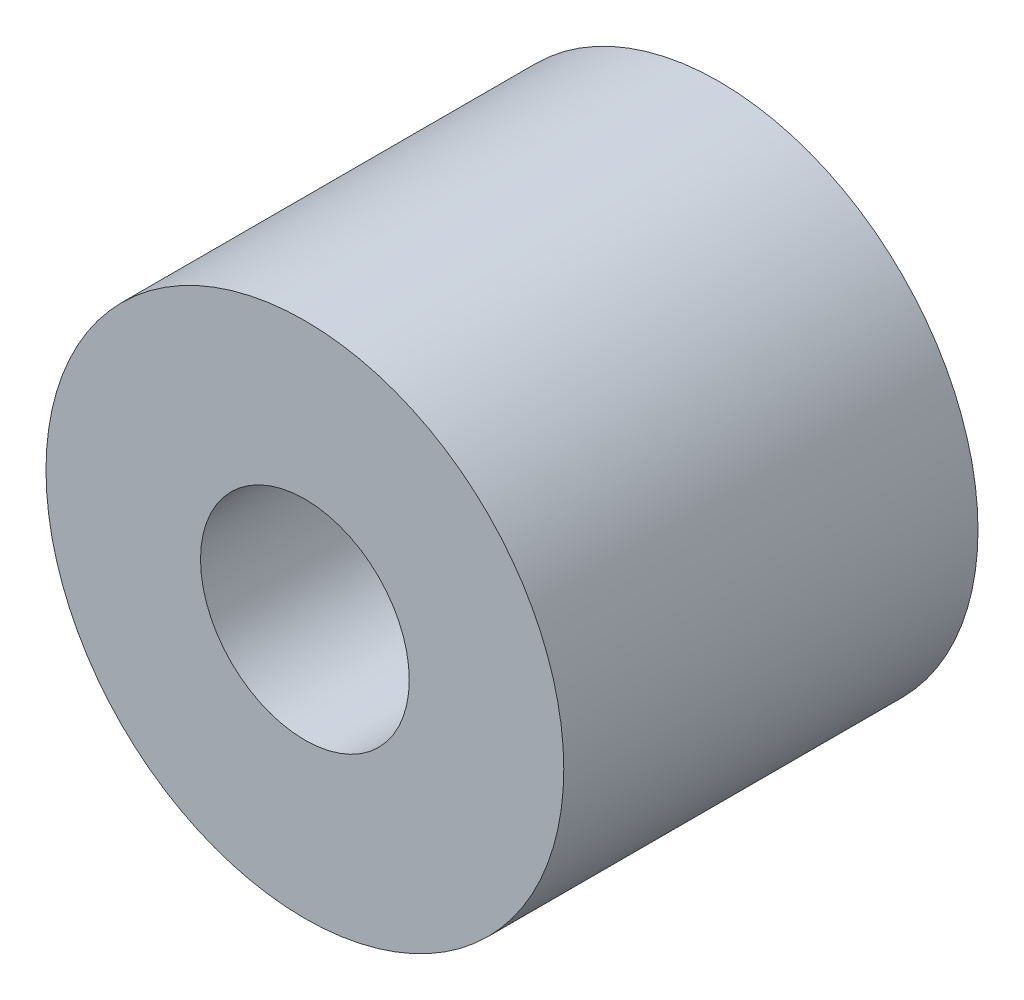
SolidWorks part; units mm, degrees
material "Nylon 101"
ref_plane "Front Plane" through (0, 0, 0) normal (0, 0, 1) x (1, 0, 0)
ref_plane "Top Plane" through (0, 0, 0) normal (0, 1, 0) x (1, 0, 0)
ref_plane "Right Plane" through (0, 0, 0) normal (1, 0, 0) x (0, 0, -1)
sketch "Sketch1" plane through (0, 0, 0) normal (0, 0, 1) x (1, 0, 0)
  circle A0 centre (0, 0) radius 7.9375
  circle A1 centre (0, 0) radius 3.2004
  dimension "OD" = 15.875
  dimension "ID" = 6.4008
extrude "Extrude1" add sketch "Sketch1" along normal mid plane 12.7
sketch "Sketch2" plane through (0, 0, 0) normal (1, 0, 0) x (0, 0, -1)
  line L0 (-6.35, -3.2004) -> (6.35, -3.2004) construction
  line L3 (6.35, 3.2004) -> (-6.35, 3.2004) construction
  line L5 (-6.35, -3.2004) -> (6.35, -3.2004)
  line L6 (6.35, 3.2004) -> (-6.35, 3.2004)
sketch "Sketch4" plane through (0, 0, 6.35) normal (0, 0, 1) x (1, 0, 0)
  line L0 (0, 0) -> (-2.263, 2.263)
  line L1 (0, -1.7463) -> (0, 1.7463) construction
  circle A0 centre (0, 0) radius 3.2004 construction
  dimension "D1" = 45
